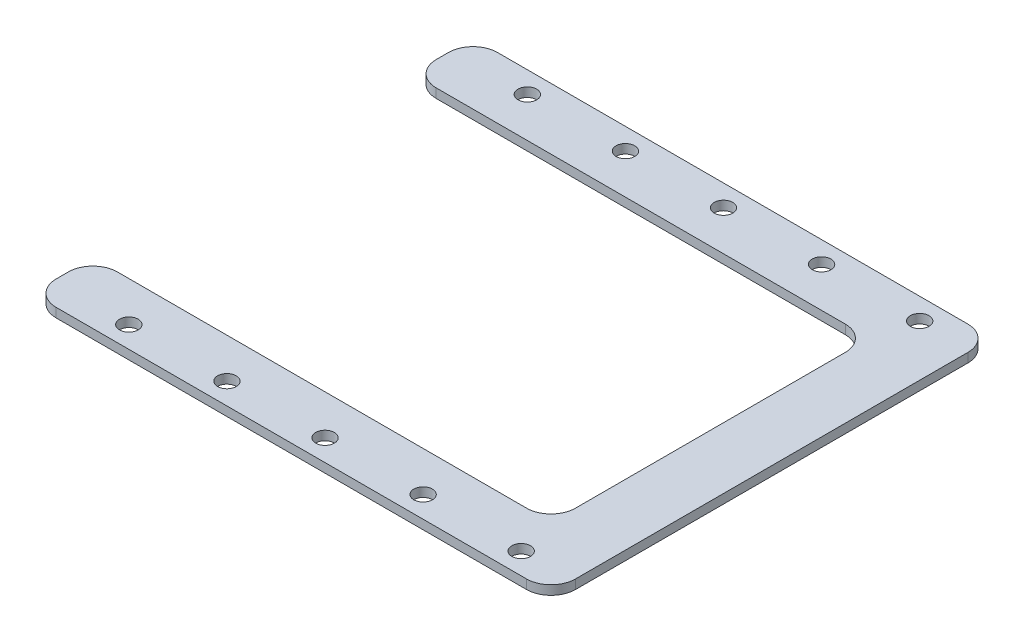
SolidWorks part; units mm, degrees
ref_plane "Front Plane" through (0, 0, 0) normal (0, 0, 1) x (1, 0, 0)
ref_plane "Top Plane" through (0, 0, 0) normal (0, 1, 0) x (1, 0, 0)
ref_plane "Right Plane" through (0, 0, 0) normal (1, 0, 0) x (0, 0, -1)
sketch "Sketch1" plane through (0, 0, 0) normal (0, 1, 0) x (1, 0, 0)
  line L0 (-76.7804, -46.0375) -> (76.7804, -46.0375) construction
  line L1 (76.7804, -57.15) -> (-76.7804, -57.15)
  line L2 (76.7804, -57.15) -> (76.7804, 57.15)
  line L3 (76.7804, 57.15) -> (-76.7804, 57.15)
  line L4 (-76.7804, -57.15) -> (-76.7804, 57.15)
  line L5 (76.7804, -57.15) -> (-76.7804, 57.15) construction
  line L6 (76.7804, 57.15) -> (-76.7804, -57.15) construction
  line L7 (60.9054, -41.275) -> (-63.1045, -41.275)
  line L8 (60.9054, -41.275) -> (60.9054, 15.875)
  line L9 (21.3279, 41.275) -> (60.9054, 41.275)
  line L10 (-63.1045, -41.275) -> (-63.1045, 41.275)
  line L11 (-76.7804, 0) -> (76.7804, 0) construction
  line L12 (21.3279, 41.275) -> (-63.1045, 41.275)
  line L13 (-76.7804, -51.5937) -> (76.7804, -51.5937) construction
  line L14 (63.5, -51.5938) -> (76.7804, -46.0375) construction
  line L15 (-63.5, -51.5938) -> (-76.7804, -46.0375) construction
  line L16 (60.9054, 41.275) -> (60.9054, 15.875)
  circle A0 centre (-63.5, -51.5938) radius 2.413
  circle A1 centre (-38.1, -51.5938) radius 2.413
  circle A2 centre (-12.7, -51.5938) radius 2.413
  circle A3 centre (12.7, -51.5938) radius 2.413
  circle A4 centre (38.1, -51.5938) radius 2.413
  circle A5 centre (63.5, -51.5938) radius 2.413
  circle A6 centre (63.5, 51.5938) radius 2.413
  circle A7 centre (38.1, 51.5938) radius 2.413
  circle A8 centre (12.7, 51.5938) radius 2.413
  circle A9 centre (-12.7, 51.5937) radius 2.413
  circle A10 centre (-38.1, 51.5937) radius 2.413
  circle A11 centre (-63.5, 51.5937) radius 2.413
  point P0 (0, 0)
  point P6 (0, 0)
  dimension "D6" = 4.826
  dimension "D8" = 25.4
  dimension "D1" = 114.3
  dimension "D2" = 153.5608
  dimension "D3" = 15.875
  dimension "D4" = 11.1125
  dimension "D5" = 5.5562
  dimension "D10" = 13.6759
  dimension "D11" = 15.875
  dimension "D7" = 6
base flange "Base-Flange1" sketch "Sketch1" thickness 2.3813 reverse thickness direction no parameters "D1"=2.3813
fillet "Fillet1" radius 6.35 4 edges at (-76.7804, -1.1906, 57.15) (-76.7804, -1.1906, -57.15) (76.7804, -1.1906, -57.15) (76.7804, -1.1906, 57.15)
sketch "Sketch7" plane through (0, -2.3813, 0) normal (0, -1, 0) x (-1, 0, 0)
  line L0 (57.7304, 57.15) -> (57.7304, -57.15)
  line L1 (-70.4304, 57.15) -> (70.4304, 57.15) construction
  line L2 (70.4304, -57.15) -> (-70.4304, -57.15) construction
  line L3 (57.7304, -57.15) -> (76.7804, -57.15)
  line L4 (76.7804, -57.15) -> (76.7804, 57.15)
  line L5 (76.7804, 57.15) -> (57.7304, 57.15)
  line L6 (76.7804, 50.8) -> (76.7804, -50.8) construction
  dimension "D1" = 0
  dimension "D2" = 19.05
extrude "Cut-Extrude2" cut sketch "Sketch7" against normal blind 2.54
fillet "Fillet2" radius 6.35 4 edges at (-57.7304, -1.1906, -57.15) (-57.7304, -1.1906, 41.275) (-57.7304, -1.1906, 57.15) (-57.7304, -1.1906, -41.275)
fillet "Fillet3" radius 6.35 2 edges at (60.9054, -1.1906, 41.275) (60.9054, -1.1906, -41.275)
sketch "Bend-Lines1" [suppressed] plane through (0, 0, 0) normal (0, 1, 0) x (1, 0, 0)
sketch "Bounding-Box1" [suppressed] plane through (0, 0, 0) normal (0, 1, 0) x (1, 0, 0)
sheet metal parameters "Sheet-Metal1" thickness 2.3813 parameters "D1"=2.3813
flat pattern "Flat-Pattern1" [suppressed]
sketch "Bend-Lines2" plane through (0, 0, 0) normal (0, 1, 0) x (1, 0, 0)
sketch "Bounding-Box2" [suppressed] plane through (0, 0, 0) normal (0, 1, 0) x (1, 0, 0)
sheet metal parameters "Sheet-Metal3" thickness 2.3813 parameters "D1"=2.3813
flat pattern "Flat-Pattern1"
sketch "Bend-Lines2" plane through (0, 0, 0) normal (0, 1, 0) x (1, 0, 0)
sketch3d "Bounding-Box2" [suppressed]
  line L0 (-57.7304, -57.15, 0) -> (76.7804, -57.15, 0) construction
  line L1 (-57.7304, 57.15, 0) -> (76.7804, 57.15, 0) construction
  line L2 (-57.7304, -57.15, 0) -> (-57.7304, 57.15, 0) construction
  line L3 (76.7804, -57.15, 0) -> (76.7804, 57.15, 0) construction
